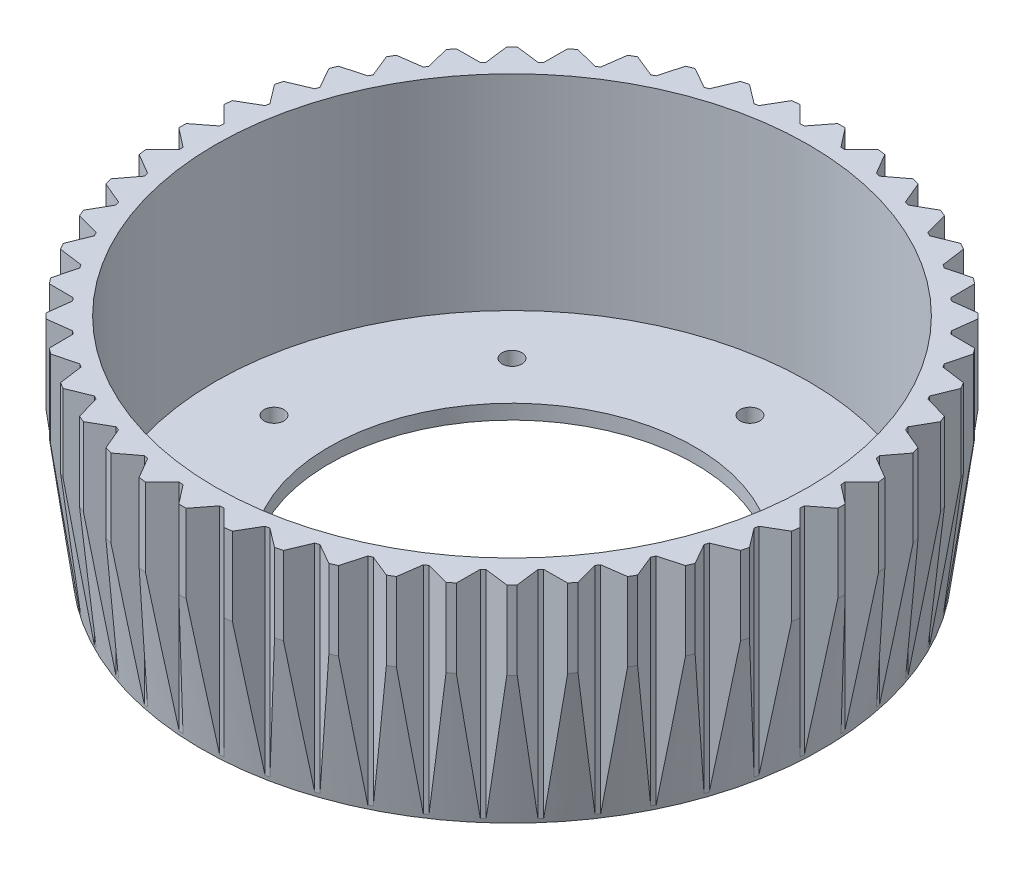
SolidWorks part; units mm, degrees
ref_plane "Front Plane" through (0, 0, 0) normal (0, 0, 1) x (1, 0, 0)
ref_plane "Top Plane" through (0, 0, 0) normal (0, 1, 0) x (1, 0, 0)
ref_plane "Right Plane" through (0, 0, 0) normal (1, 0, 0) x (0, 0, -1)
sketch "Sketch1" plane through (0, 0, 0) normal (0, 1, 0) x (1, 0, 0)
  circle A0 centre (0, 0) radius 42.5
  circle A1 centre (0, 0) radius 40.5
  circle A2 centre (0, 0) radius 25
  dimension "D1" = 85
  dimension "D2" = 2
  dimension "D3" = 50
extrude "MainBody" add sketch "Sketch1" along normal blind 30 contours A0 A1 region at (-41.2979, 0, 0)
sketch "Sketch2" plane through (0, 30, 0) normal (0, 1, 0) x (1, 0, 0)
  line L0 (-2.5, 42.4264) -> (-0.5, 45)
  line L1 (-0.5, 45) -> (0, 45)
  line L2 (0, 45) -> (0, 42.5)
  line L3 (0, 45) -> (0.5, 45)
  line L4 (0.5, 45) -> (2.5, 42.4264)
  line L5 (2.5, 42.4264) -> (-2.5, 42.4264)
  circle A0 centre (0, 0) radius 42.5 construction
  circle A1 centre (0, 0) radius 42.5 construction
  circle M9 centre (0, 0) radius 42.5
  dimension "D1" = 2.5
  dimension "D2" = 2.5
  dimension "D3" = 0.5
extrude "SingleTooth" add sketch "Sketch2" against normal blind 30 contours L2 L1 L0 M9 | L4 L3 L2 M9 | L5 M9 region at (0, 30, -42.4558) region at (-0.8586, 30, -43.4591) region at (0.8586, 30, -43.4591)
pattern_circular "ToothPattern" count 48 over 360 about axis through (0, 30, 0) along (0, 1, 0) of "SingleTooth"
extrude "Base" add sketch "Sketch1<3>" along normal blind 2 contours A1 region at (-39.3545, 0, 0)
sketch "Sketch1<3>" plane through (0, 0, 0) normal (0, 1, 0) x (1, 0, 0) same geometry as "Sketch1"
sketch "Sketch3" plane through (0, 2, 0) normal (0, 1, 0) x (1, 0, 0)
  circle A0 centre (0, 0) radius 32.5 construction
  circle A1 centre (0, 32.5) radius 1.35
  circle A2 centre (22.981, 22.981) radius 1.35
  circle A3 centre (32.5, 0) radius 1.35
  circle A4 centre (22.981, -22.981) radius 1.35
  circle A5 centre (0, -32.5) radius 1.35
  circle A6 centre (-22.981, -22.981) radius 1.35
  circle A7 centre (-32.5, 0) radius 1.35
  circle A8 centre (-22.981, 22.981) radius 1.35
  point P22 (0, 0)
  dimension "D1" = 2.7
  dimension "D3" = 65
  dimension "D2" = 8
extrude "BoltThroughHoles" cut sketch "Sketch3" against normal through all
sketch "Sketch5" plane through (0, 0, -5.3296) normal (-1, 0, 0) x (0, 0, 1)
  line L0 (-37.0968, 0) -> (-39.6704, 19.3029)
  line L3 (5.3296, 0) -> (5.3296, 17.5) construction
  line L4 (-37.0968, 30) -> (-39.6704, 30)
  line L5 (-39.6704, 30) -> (-39.6704, 0)
  line L6 (-39.6704, 0) -> (-37.0968, 0)
  line L7 (-37.0968, 0) -> (-37.0968, 30)
  line L9 (-39.6704, 19.3029) -> (-39.6704, 0)
  line L10 (-39.6704, 0) -> (-37.0968, 0)
  line L12 (-19.6704, 0) -> (30.3296, 0) construction
  line L14 (-19.6704, 0) -> (30.3296, 0)
  line L15 (-37.0968, 0) -> (-39.3502, -5)
  line L17 (-39.3502, -5) -> (-42.1704, -5)
  line L18 (-42.1704, -5) -> (-42.1704, 32.263)
  line L19 (-42.1704, 32.263) -> (-42.1704, 38.0537)
  line L20 (-39.6704, 19.3029) -> (-42.1704, 38.0537)
  dimension "D2" = 5
  dimension "D3" = 2.5
  dimension "D1" = 0
revolve "TeethTaper" cut sketch "Sketch5" angle 360 about L3 region at (0, 6.4343, -44.1421) region at (0, 11.1565, -46.1891)
